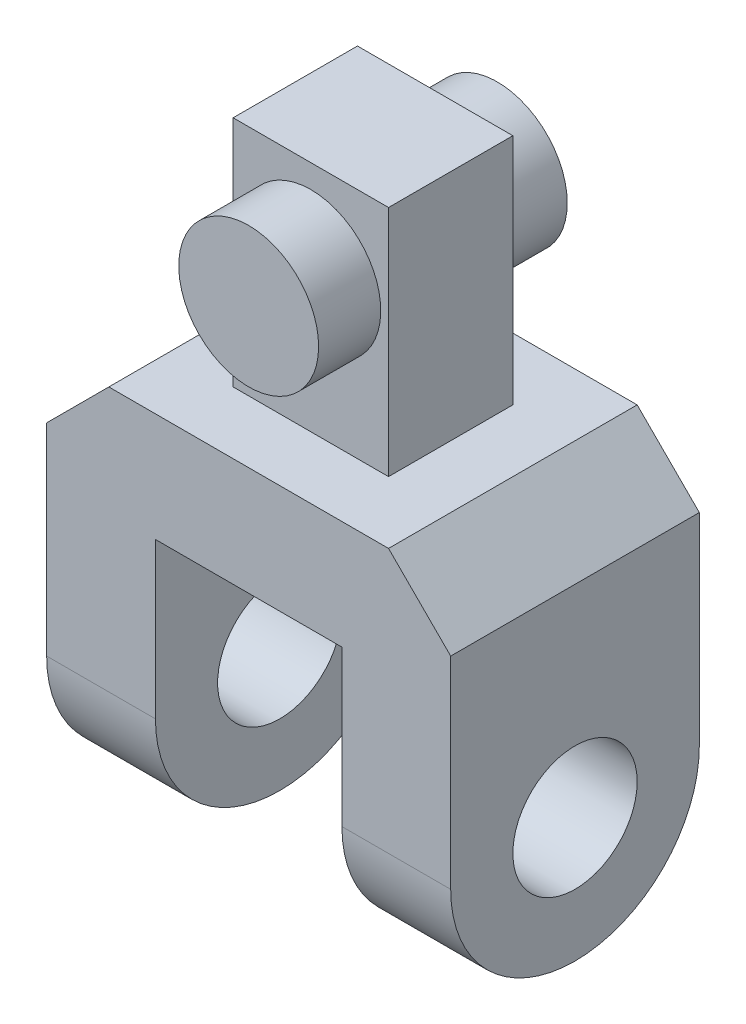
SolidWorks part; units mm, degrees
ref_plane "Front Plane" through (0, 0, 0) normal (0, 0, 1) x (1, 0, 0)
ref_plane "Top Plane" through (0, 0, 0) normal (0, 1, 0) x (1, 0, 0)
ref_plane "Right Plane" through (0, 0, 0) normal (1, 0, 0) x (0, 0, -1)
sketch "Sketch1" plane through (0, 0, 0) normal (1, 0, 0) x (0, 0, -1)
  line L0 (8, 10) -> (-8, 10)
  line L2 (-8, 0) -> (-8, 10)
  line L3 (8, 0) -> (8, 10)
  circle A0 centre (0, 0) radius 4
  arc A1 (-8, 0) -> (8, 0) centre (0, 0) ccw
  dimension "D1" = 8
  dimension "D2" = 16
  dimension "D3" = 10
extrude "Boss-Extrude1" add sketch "Sketch1" along normal blind 7 from offset 6
extrude "Boss-Extrude2" add sketch "Sketch1<2>" against normal blind 7 from offset 6 separate body offset against normal yes
sketch "Sketch1<2>" plane through (0, 0, 0) normal (1, 0, 0) x (0, 0, -1) same geometry as "Sketch1"
sketch "Sketch2" plane through (0, 10, 0) normal (0, 1, 0) x (1, 0, 0)
  line L1 (-13, 8) -> (13, 8)
  line L2 (-13, 8) -> (-13, -8)
  line L3 (-13, -8) -> (13, -8)
  line L4 (13, 8) -> (13, -8)
extrude "Boss-Extrude3" add sketch "Sketch2" along normal blind 7
chamfer "Chamfer1" distance 4 angle 45 2 edges at (13, 17, 0) (-13, 17, 0)
sketch "Sketch3" plane through (0, 17, 0) normal (0, 1, 0) x (1, 0, 0)
  line L1 (-5, -4) -> (5, -4)
  line L2 (-5, -4) -> (-5, 4)
  line L3 (-5, 4) -> (5, 4)
  line L4 (5, -4) -> (5, 4)
  point P4 (5, 0)
  point P6 (0, -4)
  dimension "D1" = 8
  dimension "D2" = 10
extrude "Boss-Extrude4" add sketch "Sketch3" along normal blind 15
sketch "Sketch5" plane through (0, 0, 0) normal (0, 0, 1) x (1, 0, 0)
  line L0 (-9, 17) -> (9, 17) construction
  circle A0 centre (0, 26) radius 4.5
  dimension "D1" = 9
  dimension "D2" = 9
extrude "Boss-Extrude5" add sketch "Sketch5" along normal mid plane 16
